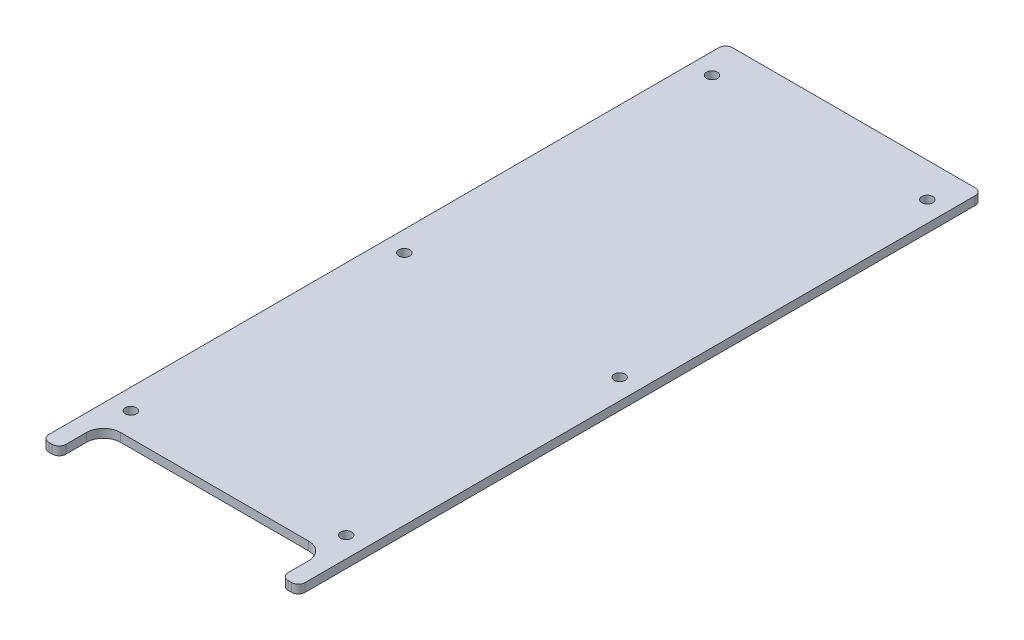
SolidWorks part; units mm, degrees
ref_plane "Front Plane" through (0, 0, 0) normal (0, 0, 1) x (1, 0, 0)
ref_plane "Top Plane" through (0, 0, 0) normal (0, 1, 0) x (1, 0, 0)
ref_plane "Right Plane" through (0, 0, 0) normal (1, 0, 0) x (0, 0, -1)
sketch "Sketch1" plane through (0, 0, 0) normal (0, 1, 0) x (1, 0, 0)
  line L0 (-39.9997, 0) -> (-39.9997, 114.3) construction
  line L1 (-47.625, 127) -> (47.625, 127)
  line L2 (-47.625, 127) -> (-47.625, -127)
  line L3 (-47.625, -127) -> (47.625, -127)
  line L4 (47.625, 127) -> (47.625, -127)
  line L5 (-47.625, 127) -> (47.625, -127) construction
  line L6 (-47.625, -127) -> (47.625, 127) construction
  line L7 (0, 0) -> (0, 127) construction
  line L8 (-39.9997, 0) -> (-39.9997, -101.6) construction
  line L9 (-39.9997, 0) -> (0, 0) construction
  line L10 (-41.275, -127) -> (-41.275, -110.49)
  line L11 (-41.275, -110.49) -> (41.275, -110.49)
  line L12 (41.275, -110.49) -> (41.275, -127)
  circle A0 centre (-39.9997, 114.3) radius 2.032
  circle A1 centre (-39.9997, 0) radius 2.032
  circle A2 centre (-39.9997, -101.6) radius 2.032
  circle A3 centre (39.9997, -101.6) radius 2.032
  circle A4 centre (39.9997, 0) radius 2.032
  circle A5 centre (39.9997, 114.3) radius 2.032
  point P0 (0, 0)
  dimension "D4" = 4.064
  dimension "D1" = 95.25
  dimension "D2" = 254
  dimension "D3" = 7.6253
  dimension "D5" = 12.7
  dimension "D6" = 25.4
  dimension "D7" = 6.35
  dimension "D8" = 6.35
  dimension "D9" = 16.51
extrude "Boss-Extrude1" add sketch "Sketch1" along normal blind 3.175 contours L4 L1 L2 L3 A4 A0 A1 A2 A3 A5 region at (0, 0, -7.0984)
fillet "Fillet1" radius 2.54 4 edges at (-47.625, 1.5875, -127) (47.625, 1.5875, -127) (47.625, 1.5875, 127) (-47.625, 1.5875, 127)
fillet "Fillet2" radius 2.54 2 edges at (41.275, 1.5875, 127) (-41.275, 1.5875, 127)
fillet "Fillet3" radius 6.35 2 edges at (41.275, 1.5875, 110.49) (-41.275, 1.5875, 110.49)
